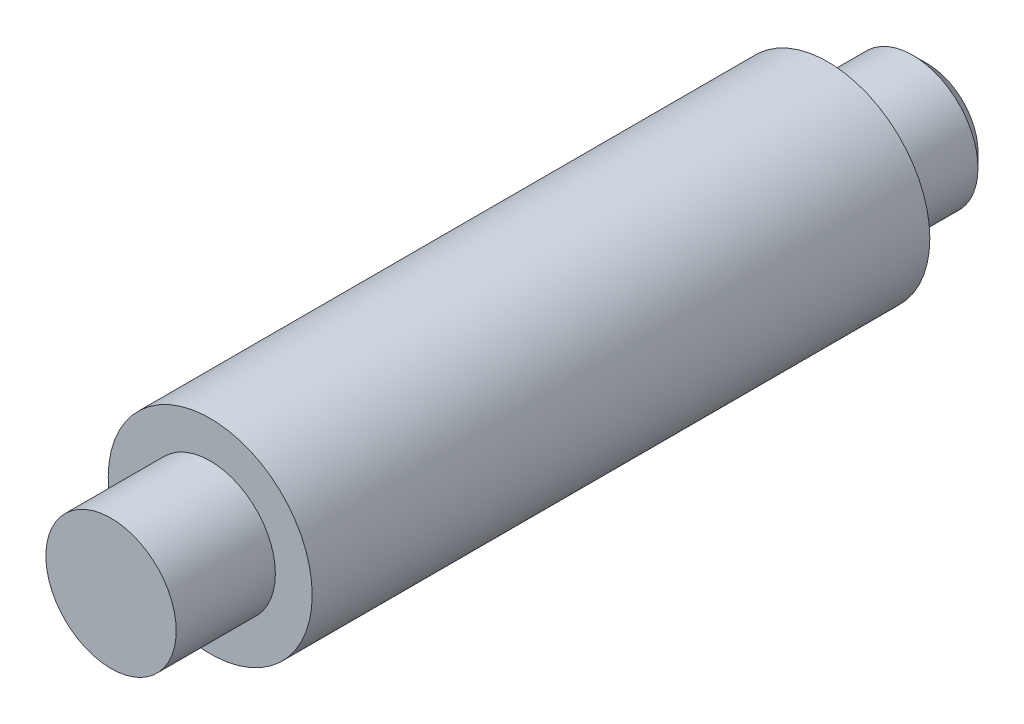
SolidWorks part; units mm, degrees
ref_plane "Front Plane" through (0, 0, 0) normal (0, 0, 1) x (1, 0, 0)
ref_plane "Top Plane" through (0, 0, 0) normal (0, 1, 0) x (1, 0, 0)
ref_plane "Right Plane" through (0, 0, 0) normal (1, 0, 0) x (0, 0, -1)
sketch "Sketch2" plane through (0, 0, 0) normal (0, 0, 1) x (1, 0, 0)
  circle A0 centre (0, 0) radius 1.25
  dimension "D1" = 2.5
sketch "Sketch3" plane through (0, 0, 0) normal (0, 0, 1) x (1, 0, 0)
  line L5 (-3.6, 3.6) -> (3.6, 3.6) construction
  line L6 (-3.6, 3.6) -> (-3.6, -3.6) construction
  line L7 (-3.6, -3.6) -> (3.6, -3.6) construction
  line L8 (3.6, 3.6) -> (3.6, -3.6) construction
  circle A0 centre (0, 0) radius 3.6
  point P4 (0, 3.6)
  point P6 (-3.6, 0)
  dimension "D1" = 7.2
extrude "Boss-Extrude1" add sketch "Sketch3" along normal blind 21.8
sketch "Sketch4" plane through (0, 0, 0) normal (0, 0, 1) x (1, 0, 0)
  circle A0 centre (0, 0) radius 2.3
  dimension "D1" = 4.6
extrude "Boss-Extrude2" add sketch "Sketch4" against normal blind 3.5
sketch "Sketch5" plane through (0, 0, 21.8) normal (0, 0, 1) x (1, 0, 0)
  circle A0 centre (0, 0) radius 2.3
  dimension "D1" = 4.6
extrude "Boss-Extrude3" add sketch "Sketch5" along normal blind 3.5
chamfer "Chamfer1" distance 0.5 angle 45 1 edges at (2.3, 0, -3.5)
equation "\"length\"=21.8"
equation "\"D1@Boss-Extrude1\"=\"length\""
equation "\"holer\"=4.6"
equation "\"D1@Sketch5\"=\"holer\""
equation "\"D1@Sketch4\"=\"holer\""
equation "\"pin\"=3.5"
equation "\"D1@Boss-Extrude2\"=\"pin\""
equation "\"D1@Boss-Extrude3\"=\"pin\""
